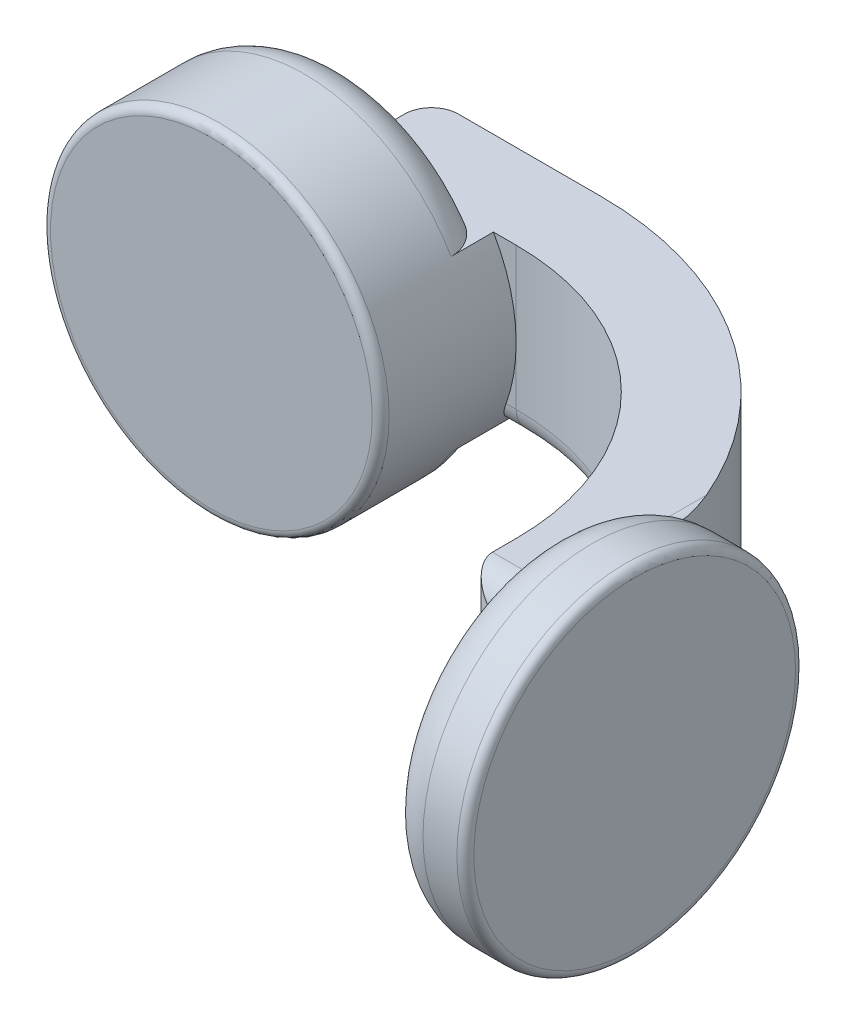
SolidWorks part; units mm, degrees
material "1060 Alloy"
ref_plane "Front Plane" through (0, 0, 0) normal (0, 0, 1) x (1, 0, 0)
ref_plane "Top Plane" through (0, 0, 0) normal (0, 1, 0) x (1, 0, 0)
ref_plane "Right Plane" through (0, 0, 0) normal (1, 0, 0) x (0, 0, -1)
sketch "Sketch4" plane through (0, 0, 0) normal (0, 0, 1) x (1, 0, 0)
  circle A0 centre (0, 0) radius 10
  dimension "D1" = 20
extrude "Boss-Extrude3" add sketch "Sketch4" along normal blind 8
sketch "Sketch5" plane through (0, 0, 0) normal (0, 1, 0) x (1, 0, 0)
  line L0 (0, 0) -> (0, 5)
  line L1 (0, 5) -> (10, 5)
  line L2 (30, -15) -> (30, -18)
  line L3 (30, -18) -> (25, -18)
  line L4 (25, -18) -> (25, -15)
  line L5 (10, 0) -> (0, 0)
  line L6 (-10, -8) -> (10, -8) construction
  line L7 (10, -8) -> (10, 0) construction
  arc A0 (10, 5) -> (30, -15) centre (10, -15) cw
  arc A1 (25, -15) -> (10, 0) centre (10, -15) ccw
  point P11 (0, 0)
  dimension "D2" = 15
  dimension "D3" = 10
  dimension "D1" = 5
extrude "Boss-Extrude4" add sketch "Sketch5" along normal mid plane 10
sketch "Sketch7" plane through (30, 0, 0) normal (1, 0, 0) x (0, 0, -1)
  line L0 (-18, 5) -> (-18, -5) construction
  circle A0 centre (-18, 0) radius 10
  dimension "D1" = 20
extrude "Boss-Extrude5" add sketch "Sketch7" along normal blind 5
fillet "Fillet4" radius 1.6 4 edges at (25, -5, 16.5) (0, 0, -5) (20.6066, -5, 4.3934) (9.3301, -5, 0)
fillet "Fillet5" radius 2.5 2 edges at (30, 0, 8) (-10, 0, 0)
fillet "Fillet6" radius 0.5 2 edges at (35, 0, 8) (10, 0, 8)
fillet "Fillet11" radius 1.6 7 edges at (25, 0.8, 18) (25.4686, -4.5314, 18) (30, 5, 16.5) (30, -5, 16.5) (28.3, -5, 18) (27.5, 5, 18) (30, 0, 18)
